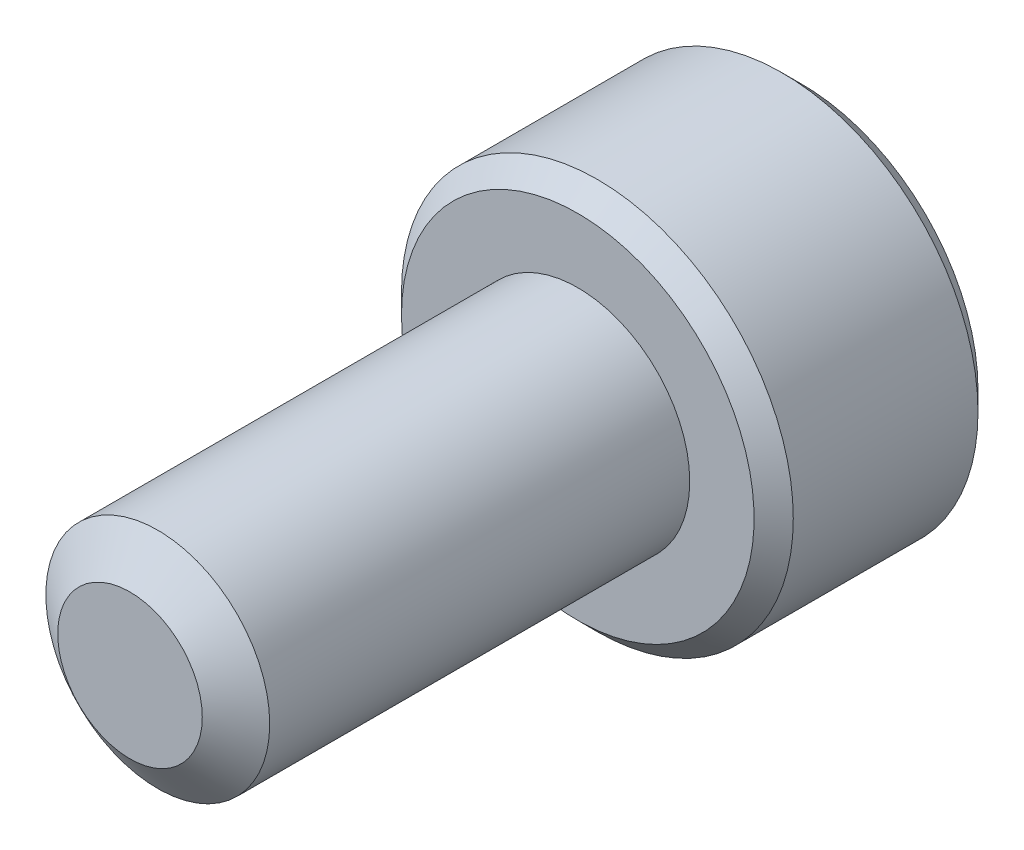
SolidWorks part; units mm, degrees
other "DetailItem1"
ref_plane "Front Plane" through (0, 0, 0) normal (0, 0, 1) x (1, 0, 0)
ref_plane "Top Plane" through (0, 0, 0) normal (0, 1, 0) x (1, 0, 0)
ref_plane "Right Plane" through (0, 0, 0) normal (1, 0, 0) x (0, 0, -1)
sketch "Sketch1" plane through (0, 0, 0) normal (0, 0, 1) x (1, 0, 0)
  circle A0 centre (0, 0) radius 2
  dimension "OD" = 4
extrude "Extrude1" add sketch "Sketch1" against normal blind 8
sketch "Sketch2" plane through (0, 0, 0) normal (0, 0, 1) x (1, 0, 0)
  circle A0 centre (0, 0) radius 2 construction
  circle A1 centre (0, 0) radius 2
curve "Helix/Spiral1" pitch 0.7 height 8.7 turns 12.4286 parameters "pitch"=0.7
sketch "Sketch3" plane through (0, 0, 0) normal (1, 0, 0) x (0, 0, -1)
  line L0 (-0.6125, 2) -> (-0.35, 1.5453)
  line L1 (-0.35, 1.5453) -> (-0.2625, 1.5453)
  line L2 (-0.2625, 1.5453) -> (0, 2)
  line L3 (-0.6125, 2) -> (0, 2)
  line L4 (-0.3062, 2) -> (-0.3062, 1.5453) construction
  line L5 (-0.4812, 1.7727) -> (-0.1312, 1.7727) construction
  line L6 (0, 2) -> (0, -2) construction
  dimension "D1" = 0.0875
  dimension "D2" = 0.35
  dimension "D3" = 60
sweep "Cut-Sweep1" [suppressed] cut profiles "Sketch3" path "Helix/Spiral1"
sketch "Sketch4" plane through (0, 0, 0) normal (1, 0, 0) x (0, 0, -1)
  line L0 (0.4962, 2) -> (0, 1.2913)
  line L1 (0, 1.2913) -> (0, 2)
  line L2 (0.4962, 2) -> (0, 2)
  line L3 (-0.6125, 2) -> (0, 2) construction
  line L4 (0, 0) -> (7.0209, 0) construction
  dimension "D1" = 55
  dimension "D2" = 0.254
revolve "Cut-Revolve1" cut sketch "Sketch4" angle 360 about L4
sketch "Sketch6" plane through (0, 0, -8) normal (0, 0, -1) x (-1, 0, 0)
  circle A0 centre (0, 0) radius 3.5
  dimension "head dia" = 7
extrude "Extrude2" add sketch "Sketch6" along normal blind 4
sketch "Sketch7" plane through (0, 0, -12) normal (0, 0, -1) x (-1, 0, 0)
  line L1 (0, 1.7321) -> (-1.5, 0.866)
  line L2 (-1.5, 0.866) -> (-1.5, -0.866)
  line L3 (-1.5, -0.866) -> (0, -1.7321)
  line L4 (0, -1.7321) -> (1.5, -0.866)
  line L5 (1.5, -0.866) -> (1.5, 0.866)
  line L6 (1.5, 0.866) -> (0, 1.7321)
  circle A0 centre (0, 0) radius 1.5 construction
  dimension "hex dia" = 3
extrude "Cut-Extrude1" cut sketch "Sketch7" against normal blind 2.25
sketch "Sketch8" plane through (0, 0, -12) normal (0, 0, -1) x (-1, 0, 0)
  circle A0 centre (0, 0) radius 1.7321
extrude "Cut-Extrude2" cut sketch "Sketch8" against normal through all draft 45
chamfer "Chamfer1" distance 0.35 angle 45 2 edges at (-3.5, 0, -12) (-3.5, 0, -8)
sketch "Sketch10" plane through (0, 0, -8) normal (0, 0, 1) x (1, 0, 0)
  circle A1 centre (0, 0) radius 2
  circle A2 centre (0, 0) radius 2
  dimension "D1" = 0
ref_plane "Plane1" through (0, 0, 0) normal (0, 0, 1) x (1, 0, 0)
extrude "partial thread" [suppressed] add sketch "Sketch10" along normal up to surface (10 mm away) separate body up to plane "Plane1"
chamfer "Chamfer2" [suppressed] distance 0.08 angle 45
combine bodies "Combine1" [suppressed] operation type add bodies to combine 107 108
sketch "Sketch9" plane through (0, 0, 0) normal (1, 0, 0) x (0, 0, -1)
  line L0 (0, 2) -> (0, -2) construction
  line L1 (1.75, 2) -> (1.75, -2) construction
  dimension "D1" = 1.75
equation "\"D3@Helix/Spiral1\" = \"screw length@Extrude1\"+\"pitch@Helix/Spiral1\""
equation "\"D1@Sketch3\" = \"pitch@Helix/Spiral1\"*.125"
equation "\"D2@Sketch3\" = \"pitch@Helix/Spiral1\"*.5"
equation "\"D1@Cut-Extrude1\" = \"hex dia@Sketch7\"*.75"
equation "\"D1@Chamfer1\" = \"head dia@Sketch6\"*.05"
equation "\"D1@Sketch9\" = \"pitch@Helix/Spiral1\"*2.5"
equation "\"D1@Chamfer2\"=\"OD@Sketch1\"*.02"
